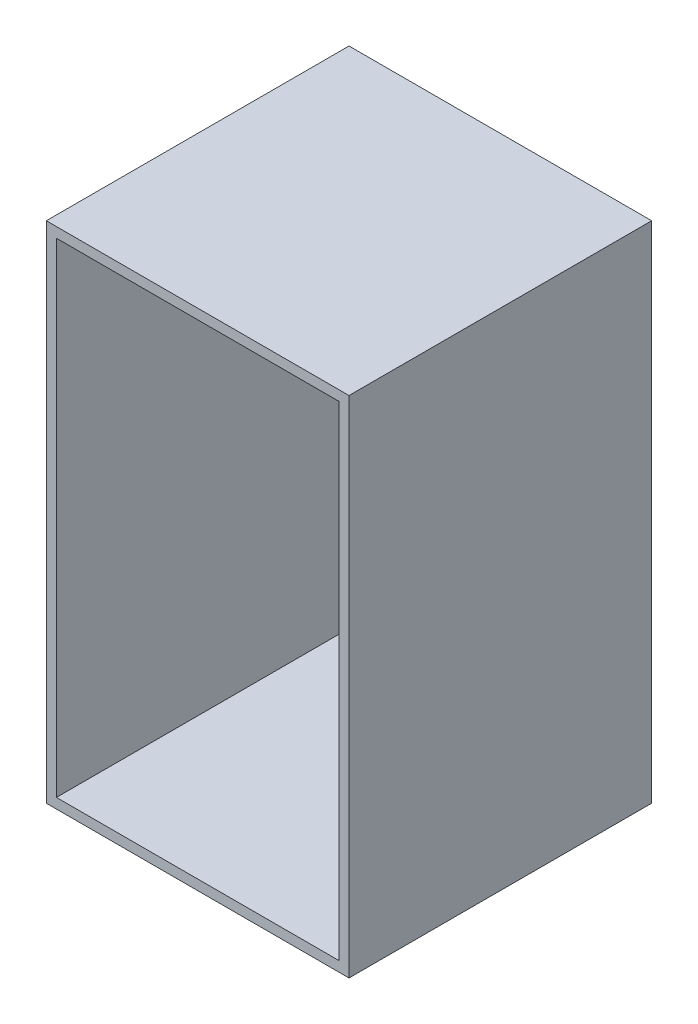
SolidWorks part; units mm, degrees
note: '?' marks a value the reader was unsure of.
ref_plane "Front Plane" through (0, 0, 0) normal (0, 0, 1) x (1, 0, 0)
ref_plane "Top Plane" through (0, 0, 0) normal (0, 1, 0) x (1, 0, 0)
ref_plane "Right Plane" through (0, 0, 0) normal (1, 0, 0) x (0, 0, -1)
sketch "Sketch1" plane through (0, 0, 0) normal (0, 1, 0) x (1, 0, 0)
  line L1 (-38.1, -38.1) -> (38.1, -38.1)
  line L2 (-38.1, -38.1) -> (-38.1, 38.1)
  line L3 (-38.1, 38.1) -> (38.1, 38.1)
  line L4 (38.1, -38.1) -> (38.1, 38.1)
  line L5 (-38.1, -38.1) -> (38.1, 38.1) construction
  line L6 (-38.1, 38.1) -> (38.1, -38.1) construction
  point P0 (0, 0)
  dimension "D1" = 76.2
  dimension "D2" = 76.2
extrude "box" add sketch "Sketch1" along normal blind 127
shell "hollow it" thickness 2.54
sketch "Sketch2" plane through (0, 0, -38.1) normal (0, 0, -1) x (-1, 0, 0)
  line L0 (-38.1, 127) -> (38.1, 127) construction
  line L1 (-29.21, 69.85) -> (-24.892, 69.85)
  line L2 (-29.21, 69.85) -> (-29.21, 6.35)
  line L3 (-29.21, 6.35) -> (-24.892, 6.35)
  line L4 (-24.892, 69.85) -> (-24.892, 6.35)
  line L6 (-38.1, 127) -> (-38.1, 0) construction
  dimension "D1" = 4.318
  dimension "D2" = 63.5
  dimension "D3" = 57.15
  dimension "D4" = 8.89
extrude "slider track" cut sketch "Sketch2" against normal up to surface (2.54 mm away) up to face at (0, 63.5, -35.56)
sketch "Sketch6" plane through (0, 0, -38.1) normal (0, 0, -1) x (-1, 0, 0)
  line L0 (-3.2977, 45.72) -> (-3.2977, 52.07)
  line L1 (-3.2977, 52.07) -> (3.0523, 52.07)
  line L2 (3.0523, 52.07) -> (3.0523, 45.72)
  line L3 (3.0523, 45.72) -> (9.4023, 45.72)
  line L4 (9.4023, 45.72) -> (9.4023, 39.37)
  line L5 (9.4023, 39.37) -> (3.0523, 39.37)
  line L6 (3.0523, 39.37) -> (3.0523, 33.02)
  line L7 (3.0523, 33.02) -> (-3.2977, 33.02)
  line L8 (-3.2977, 33.02) -> (-3.2977, 39.37)
  line L9 (-3.2977, 39.37) -> (-9.6477, 39.37)
  line L10 (-9.6477, 39.37) -> (-9.6477, 45.72)
  line L11 (-9.6477, 45.72) -> (-3.2977, 45.72)
  line L12 (-38.1, 0) -> (38.1, 0) construction
  dimension "D1" = 6.35
  dimension "D2" = 6.35
  dimension "D3" = 6.35
  dimension "D4" = 6.35
  dimension "D5" = 6.35
  dimension "D6" = 6.35
  dimension "D7" = 6.35
  dimension "D8" = 6.35
  dimension "D9" = 6.35
  dimension "D10" = 33.02
extrude "dpad large shape" cut sketch "Sketch6" against normal blind 1.27
sketch "Sketch7" plane through (0, 0, -36.83) normal (0, 0, -1) x (-1, 0, 0)
  line L0 (-3.2977, 45.72) -> (-9.6477, 45.72) construction
  line L1 (-9.6477, 45.72) -> (-9.6477, 39.37) construction
  line L2 (3.0523, 33.02) -> (3.0523, 39.37) construction
  line L3 (-3.2977, 33.02) -> (3.0523, 33.02) construction
  line L4 (3.0523, 39.37) -> (9.4023, 39.37) construction
  line L5 (9.4023, 39.37) -> (9.4023, 45.72) construction
  line L6 (3.0523, 45.72) -> (3.0523, 52.07) construction
  line L7 (-3.2977, 52.07) -> (-3.2977, 45.72) construction
  line L8 (3.0523, 52.07) -> (-3.2977, 52.07) construction
  circle A0 centre (-0.1227, 48.895) radius 2.794
  circle A1 centre (6.2273, 42.672) radius 2.794
  circle A2 centre (-0.1227, 36.195) radius 2.794
  circle A3 centre (-6.4727, 42.545) radius 2.794
  point P12 (3.0523, 36.195)
  point P17 (6.2273, 39.37)
  dimension "D3" = 5.588
  dimension "D6" = 5.588
  dimension "D9" = 5.588
  dimension "D13" = 5.588
  dimension "D1" = 3.175
  dimension "D2" = 3.175
  dimension "D4" = 3.175
  dimension "D5" = 3.175
  dimension "D7" = 3.302
  dimension "D8" = 3.175
  dimension "D10" = 3.175
  dimension "D11" = 3.175
  dimension "D12" = 3.175
extrude "dpad tiny holes" cut sketch "Sketch7" against normal blind 1.27
sketch "Sketch8" plane through (0, 0, -38.1) normal (0, 0, -1) x (-1, 0, 0)
  line L0 (38.1, 127) -> (38.1, 0) construction
  line L1 (-38.1, 127) -> (38.1, 127) construction
  circle A0 centre (20.32, 19.05) radius 12.7
  dimension "D1" = 25.4
  dimension "D2" = 17.78
  dimension "D3" = 107.95
extrude "dial large ring" cut sketch "Sketch8" against normal blind 1.27
ref_point "dial center"
sketch "Sketch9" plane through (0, 0, -36.83) normal (0, 0, -1) x (-1, 0, 0)
  circle A0 centre (20.32, 19.05) radius 5.08
  dimension "D1" = 10.16
extrude "dial small hole" cut sketch "Sketch9" against normal blind 1.27
sketch "Sketch12" plane through (0, 0, -38.1) normal (0, 0, -1) x (-1, 0, 0)
  line L0 (38.1, 127) -> (38.1, 0) construction
  line L1 (-11.43, 30.48) -> (-2.54, 30.48)
  line L2 (-11.43, 30.48) -> (-11.43, 5.08)
  line L3 (-11.43, 5.08) -> (-2.54, 5.08)
  line L4 (-2.54, 30.48) -> (-2.54, 5.08)
  line L5 (-38.1, 0) -> (38.1, 0) construction
  dimension "D1" = 25.4
  dimension "D2" = 8.89
  dimension "D3" = 40.64
  dimension "D4" = 5.08
extrude "hole for scroll wheel" cut sketch "Sketch12" against normal blind 2.54
sketch "Sketch14" plane through (2.54, 0, 0) normal (1, 0, 0) x (0, 0, -1)
  line L0 (38.1, 5.08) -> (38.1, 30.48) construction
  circle A0 centre (38.1, 17.78) radius 6.35
extrude "nibble base 1" add sketch "Sketch14" against normal blind 5.08
sketch "Sketch15" plane through (11.43, 0, 0) normal (-1, 0, 0) x (0, 0, 1)
  line L0 (-38.1, 30.48) -> (-38.1, 5.08) construction
  circle A0 centre (-38.1, 17.78) radius 6.35
extrude "nibble base 2" add sketch "Sketch15" against normal blind 5.08
sketch "Sketch16" plane through (11.43, 0, 0) normal (-1, 0, 0) x (0, 0, 1)
  circle A0 centre (-38.1, 17.78) radius 3.302
extrude "nibble holes" cut sketch "Sketch16" against normal up to surface and the other way up to surface up to face at (16.51, 17.78, -41.275) other way up to face at (-2.54, 17.78, -41.275)
sketch "Sketch17" plane through (0, 0, -38.1) normal (0, 0, -1) x (-1, 0, 0)
  line L0 (31.75, 65.405) -> (31.75, 61.595) construction
  line L1 (33.782, 65.405) -> (33.782, 61.595)
  line L2 (29.718, 65.405) -> (29.718, 61.595)
  line L3 (-38.1, 0) -> (38.1, 0) construction
  line L4 (38.1, 127) -> (38.1, 0) construction
  arc A0 (33.782, 65.405) -> (29.718, 65.405) centre (31.75, 65.405) ccw
  arc A1 (29.718, 61.595) -> (33.782, 61.595) centre (31.75, 61.595) ccw
  point P2 (31.75, 63.5)
  point P11 (25.4, 63.5)
  dimension "D1" = 2.032
  dimension "D2" = 3.81
  dimension "D3" = 63.5
  dimension "D4" = 6.35
  dimension "D5" = 6.35
ref_axis "axis of button" through (-25.4, 63.5, -38.1) along (0, 0, -1)?
extrude "single button leg hole" cut sketch "Sketch17" against normal blind 2.54
pattern_circular "moar leg holes" count 4 over 360 about axis through (-25.4, 63.5, 0) along (0, 0, 1) of "single button leg hole"
sketch "Sketch19" plane through (0, 0, -38.1) normal (0, 0, -1) x (-1, 0, 0)
  line L0 (-38.1, 0) -> (38.1, 0) construction
  line L1 (-22.86, 121.4316) -> (22.86, 121.4316)
  line L2 (-22.86, 121.4316) -> (-22.86, 75.7116)
  line L3 (-22.86, 75.7116) -> (22.86, 75.7116)
  line L4 (22.86, 121.4316) -> (22.86, 75.7116)
  line L5 (-22.86, 121.4316) -> (22.86, 75.7116) construction
  line L6 (-22.86, 75.7116) -> (22.86, 121.4316) construction
  point P0 (0, 98.5716)
  point P5 (0, 0)
  dimension "D1" = 45.72
  dimension "D2" = 45.72
  dimension "D3" = 0
extrude "base for joystick" add sketch "Sketch19" along normal blind 3.81 and the other way blind 15.24
ref_point "joystick center"
sketch "Sketch21" plane through (0, 0, -41.91) normal (0, 0, -1) x (-1, 0, 0)
  line L1 (20.32, 78.2516) -> (-20.32, 78.2516)
  line L2 (20.32, 78.2516) -> (20.32, 118.8916)
  line L3 (20.32, 118.8916) -> (-20.32, 118.8916)
  line L4 (-20.32, 78.2516) -> (-20.32, 118.8916)
  line L5 (20.32, 78.2516) -> (-20.32, 118.8916) construction
  line L6 (20.32, 118.8916) -> (-20.32, 78.2516) construction
  point P0 (0, 98.5716)
  dimension "D1" = 2.54
  dimension "D2" = 2.54
extrude "joystick hole" cut sketch "Sketch21" against normal through all
ref_point "joystick small nibbles"
ref_point "joystick large nibbles"
sketch "Sketch22" plane through (-20.32, 0, 0) normal (1, 0, 0) x (0, 0, -1)
  circle A0 centre (32.385, 98.5716) radius 3.175
  dimension "D1" = 6.35
extrude "large nibbles" cut sketch "Sketch22" against normal up to surface and the other way up to surface up to face at (-22.86, 98.5716, -40.005) other way up to face at (22.86, 98.5716, -40.005)
sketch "Sketch23" plane through (0, 118.8916, 0) normal (0, -1, 0) x (1, 0, 0)
  circle A0 centre (0, -32.385) radius 4.445
  dimension "D1" = 8.89
extrude "small nibbles" cut sketch "Sketch23" against normal up to surface and the other way offset from surface (48.26 mm away) 5.08 up to face at (0, 124.46, 1.27) other way up to face at (0, 75.7116, -29.21)
